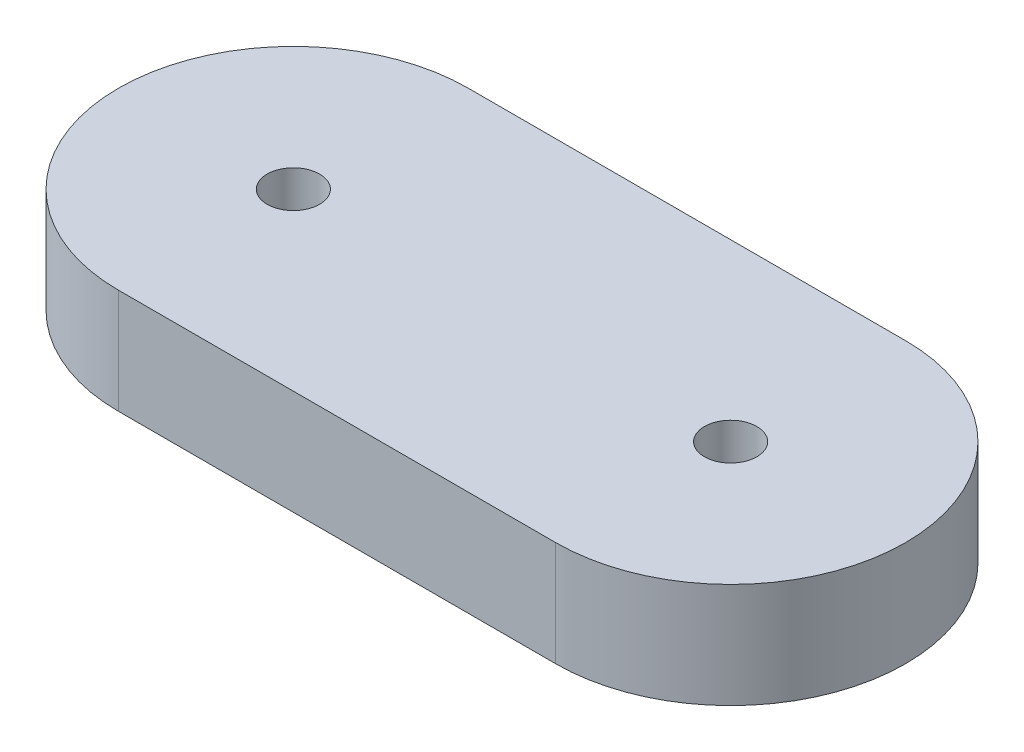
SolidWorks part; units mm, degrees
ref_plane "Front Plane" through (0, 0, 0) normal (0, 0, 1) x (1, 0, 0)
ref_plane "Top Plane" through (0, 0, 0) normal (0, 1, 0) x (1, 0, 0)
ref_plane "Right Plane" through (0, 0, 0) normal (1, 0, 0) x (0, 0, -1)
sketch "Sketch1" plane through (0, 0, 0) normal (0, 1, 0) x (1, 0, 0)
  line L0 (-12.5, 0) -> (12.5, 0) construction
  line L1 (-55, 0) -> (55, 0) construction
  line L2 (-12.5, 10) -> (0, 10)
  line L3 (-12.5, -10) -> (0, -10)
  line L4 (-11, 10) -> (-11, -10) construction
  line L5 (-6, 10) -> (-6, -10) construction
  line L6 (0, 10) -> (0, -10)
  line L9 (0, -6.6834) -> (0, 6.6834) construction
  arc A0 (-12.5, 10) -> (-12.5, -10) centre (-12.5, 0) ccw
  circle A3 centre (-12.5, 0) radius 1.5
  circle A4 centre (0, 0) radius 6 construction
  point P5 (0, 0)
  point P7 (0, 6)
  dimension "D1" = 3
  dimension "D2" = 12
  dimension "D4" = 4
  dimension "D3" = 25
extrude "Boss-Extrude1" add sketch "Sketch1" along normal blind 6
mirror "Mirror1" about plane through (0, 6, -10) normal (-1, 0, 0) of "Boss-Extrude1"
equation "\"M3_d\"= \"M3_d_laser@troublemaker.Assembly\""
equation "\"rod_z_d\"= 12"
equation "\"t\"=4"
equation "\"t2\"= 5"
equation "\"D1@Sketch1\"=\"M3_d\""
equation "\"D2@Sketch1\"=\"rod_z_d\""
equation "\"D4@Sketch1\"=\"t\""
equation "\"housing_t\"= \"housing_t_glob@troublemaker.Assembly\""
equation "\"D1@Boss-Extrude1\"=\"housing_t\""
